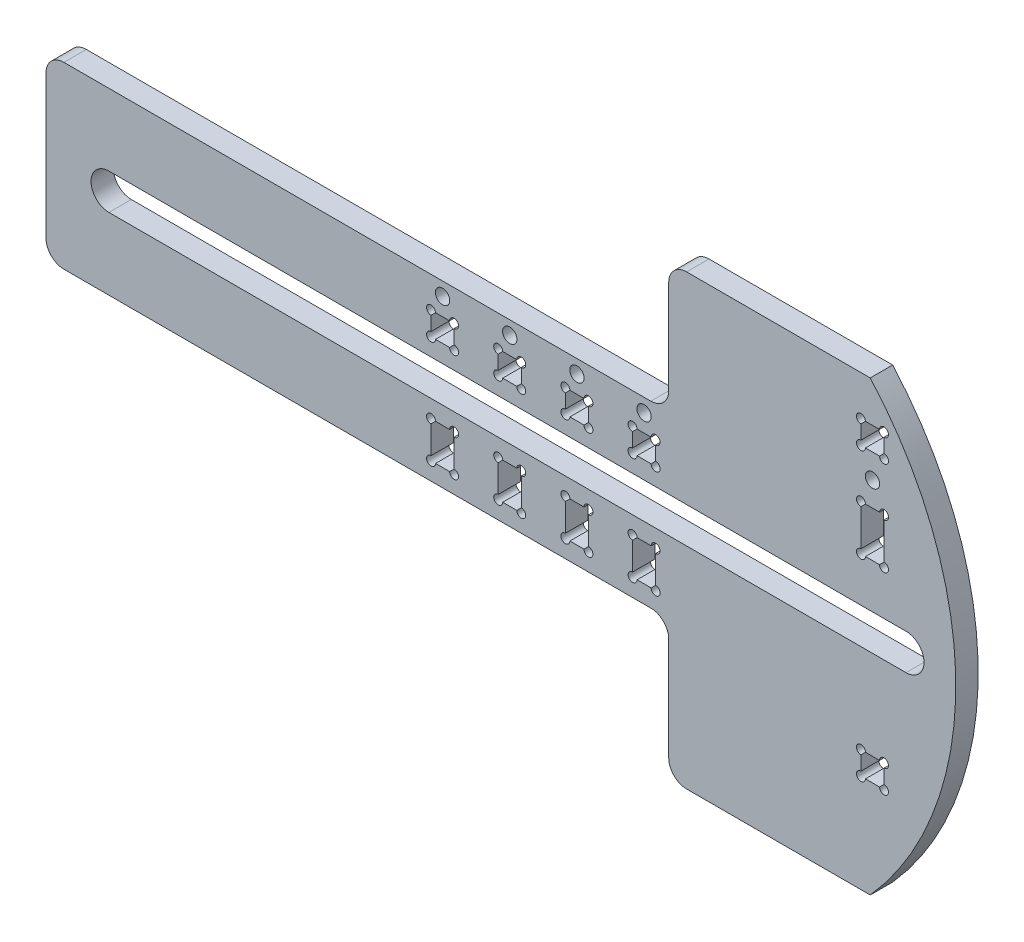
SolidWorks part; units mm, degrees
material "Somente - Acrílico Extrudado"
ref_plane "Front Plane" through (0, 0, 0) normal (0, 0, 1) x (1, 0, 0)
ref_plane "Top Plane" through (0, 0, 0) normal (0, 1, 0) x (1, 0, 0)
ref_plane "Right Plane" through (0, 0, 0) normal (1, 0, 0) x (0, 0, -1)
sketch "Esboço1" plane through (0, 0, 0) normal (0, 0, 1) x (1, 0, 0)
  line L181 (42.9065, -57.2479) -> (42.9065, -34.2586)
  line L182 (38.9065, -30.2586) -> (-92.1466, -30.2586)
  line L183 (-96.1466, -26.2586) -> (-96.1466, 5.7521)
  line L184 (-92.1466, 9.7521) -> (38.9065, 9.7521)
  line L185 (42.9065, 13.7521) -> (42.9065, 34.7521)
  line L186 (46.9065, 38.7521) -> (87.9065, 38.7521)
  line L187 (87.9065, -61.2479) -> (46.9065, -61.2479)
  line L188 (-82.0916, -6.2479) -> (95.9065, -6.2479)
  line L189 (95.9065, -14.2479) -> (-82.0935, -14.2479)
  line L190 (39.9815, 2.8271) -> (34.8315, 2.8271)
  line L191 (34.8315, 2.8271) -> (34.8315, -2.3229)
  line L192 (34.8315, -2.3229) -> (39.9815, -2.3229)
  line L193 (39.9815, -2.3229) -> (39.9815, 2.8271)
  line L194 (85.8315, 3.6771) -> (90.9815, 3.6771)
  line L195 (90.9815, 3.6771) -> (90.9815, 13.8271)
  line L196 (90.9815, 13.8271) -> (85.8315, 13.8271)
  line L197 (85.8315, 13.8271) -> (85.8315, 3.6771)
  line L198 (85.8315, -39.3229) -> (90.9815, -39.3229)
  line L199 (90.9815, -39.3229) -> (90.9815, -34.1729)
  line L200 (90.9815, -34.1729) -> (85.8315, -34.1729)
  line L201 (85.8315, -34.1729) -> (85.8315, -39.3229)
  line L202 (34.8315, -26.3229) -> (39.9815, -26.3229)
  line L203 (39.9815, -26.3229) -> (39.9815, -18.1729)
  line L204 (39.9815, -18.1729) -> (34.8315, -18.1729)
  line L205 (34.8315, -18.1729) -> (34.8315, -26.3229)
  line L206 (85.8315, 24.6771) -> (90.9815, 24.6771)
  line L207 (90.9815, 24.6771) -> (90.9815, 29.8271)
  line L208 (90.9815, 29.8271) -> (85.8315, 29.8271)
  line L209 (85.8315, 29.8271) -> (85.8315, 24.6771)
  line L210 (19.9065, -26.2479) -> (24.9065, -26.2479) construction
  line L211 (24.9065, -26.2479) -> (24.9065, -18.2479) construction
  line L212 (24.9065, -18.2479) -> (19.9065, -18.2479) construction
  line L213 (19.9065, -18.2479) -> (19.9065, -26.2479) construction
  line L214 (19.9065, -2.2479) -> (24.9065, -2.2479) construction
  line L215 (24.9065, -2.2479) -> (24.9065, 2.7521) construction
  line L216 (24.9065, 2.7521) -> (19.9065, 2.7521) construction
  line L217 (19.9065, 2.7521) -> (19.9065, -2.2479) construction
  line L218 (4.9065, 2.7521) -> (4.9065, -2.2479) construction
  line L219 (4.9065, -2.2479) -> (9.9065, -2.2479) construction
  line L220 (9.9065, -2.2479) -> (9.9065, 2.7521) construction
  line L221 (9.9065, 2.7521) -> (4.9065, 2.7521) construction
  line L222 (4.9065, -26.2479) -> (9.9065, -26.2479) construction
  line L223 (9.9065, -26.2479) -> (9.9065, -18.2479) construction
  line L224 (9.9065, -18.2479) -> (4.9065, -18.2479) construction
  line L225 (4.9065, -18.2479) -> (4.9065, -26.2479) construction
  line L226 (-10.0935, -26.2479) -> (-5.0935, -26.2479) construction
  line L227 (-5.0935, -26.2479) -> (-5.0935, -18.2479) construction
  line L228 (-5.0935, -18.2479) -> (-10.0935, -18.2479) construction
  line L229 (-10.0935, -18.2479) -> (-10.0935, -26.2479) construction
  line L230 (-10.0935, -2.2479) -> (-5.0935, -2.2479) construction
  line L231 (-5.0935, -2.2479) -> (-5.0935, 2.7521) construction
  line L232 (-5.0935, 2.7521) -> (-10.0935, 2.7521) construction
  line L233 (-10.0935, 2.7521) -> (-10.0935, -2.2479) construction
  line L234 (24.9815, 2.8271) -> (19.8315, 2.8271)
  line L235 (19.8315, 2.8271) -> (19.8315, -2.3229)
  line L236 (19.8315, -2.3229) -> (24.9815, -2.3229)
  line L237 (24.9815, -2.3229) -> (24.9815, 2.8271)
  line L238 (19.8315, -26.3229) -> (24.9815, -26.3229)
  line L239 (24.9815, -26.3229) -> (24.9815, -18.1729)
  line L240 (24.9815, -18.1729) -> (19.8315, -18.1729)
  line L241 (19.8315, -18.1729) -> (19.8315, -26.3229)
  line L242 (9.9815, 2.8271) -> (4.8315, 2.8271)
  line L243 (4.8315, 2.8271) -> (4.8315, -2.3229)
  line L244 (4.8315, -2.3229) -> (9.9815, -2.3229)
  line L245 (9.9815, -2.3229) -> (9.9815, 2.8271)
  line L246 (4.8315, -26.3229) -> (9.9815, -26.3229)
  line L247 (9.9815, -26.3229) -> (9.9815, -18.1729)
  line L248 (9.9815, -18.1729) -> (4.8315, -18.1729)
  line L249 (4.8315, -18.1729) -> (4.8315, -26.3229)
  line L250 (-5.0185, 2.8271) -> (-10.1685, 2.8271)
  line L251 (-10.1685, 2.8271) -> (-10.1685, -2.3229)
  line L252 (-10.1685, -2.3229) -> (-5.0185, -2.3229)
  line L253 (-5.0185, -2.3229) -> (-5.0185, 2.8271)
  line L254 (-10.1685, -26.3229) -> (-5.0185, -26.3229)
  line L255 (-5.0185, -26.3229) -> (-5.0185, -18.1729)
  line L256 (-5.0185, -18.1729) -> (-10.1685, -18.1729)
  line L257 (-10.1685, -18.1729) -> (-10.1685, -26.3229)
  circle A1 centre (7.4065, 6.7521) radius 1.5 construction
  circle A2 centre (22.4065, 6.7521) radius 1.5 construction
  circle A3 centre (-7.5935, 6.7521) radius 1.5 construction
  circle A4 centre (37.4065, 6.7521) radius 1.5
  arc A5 (42.9065, -34.2586) -> (38.9065, -30.2586) centre (38.9065, -34.2586) ccw
  arc A6 (-96.1466, -26.2586) -> (-92.1466, -30.2586) centre (-92.1466, -26.2586) ccw
  arc A7 (-92.1466, 9.7521) -> (-96.1466, 5.7521) centre (-92.1466, 5.7521) ccw
  arc A8 (38.9065, 9.7521) -> (42.9065, 13.7521) centre (38.9065, 13.7521) ccw
  arc A9 (46.9065, 38.7521) -> (42.9065, 34.7521) centre (46.9065, 34.7521) ccw
  arc A10 (87.9065, -61.2479) -> (87.9065, 38.7521) centre (32.0381, -11.2479) ccw
  arc A11 (42.9065, -57.2479) -> (46.9065, -61.2479) centre (46.9065, -57.2479) ccw
  arc A12 (-82.0916, -6.2479) -> (-82.0935, -14.2479) centre (-82.0935, -10.2479) ccw
  arc A13 (95.9065, -14.2479) -> (95.9065, -6.2479) centre (95.9065, -10.2479) ccw
  circle A14 centre (88.4065, 19.2521) radius 1.5
  circle A15 centre (22.4065, 6.7521) radius 1.5
  circle A16 centre (7.4065, 6.7521) radius 1.5
  circle A17 centre (-7.5935, 6.7521) radius 1.5
  dimension "D1" = 4
base flange "Flange-base1" sketch "Esboço1" thickness 5 reverse thickness direction no parameters "D1"=0.1
sketch "Esboço2" plane through (0, 0, 0) normal (0, 0, 1) x (1, 0, 0)
  line L0 (39.9815, -2.3229) -> (39.9815, 2.8271) construction
  line L1 (34.8315, -2.3229) -> (39.9815, -2.3229) construction
  circle A0 centre (90.9815, 29.8271) radius 1
  circle A1 centre (85.8315, 29.8271) radius 1
  circle A2 centre (85.8315, 24.6771) radius 1
  circle A3 centre (90.9815, 24.6771) radius 1
  circle A4 centre (90.9815, 13.8271) radius 1
  circle A5 centre (85.8315, 13.8271) radius 1
  circle A6 centre (90.9815, 3.6771) radius 1
  circle A7 centre (85.8315, 3.6771) radius 1
  circle A8 centre (85.8315, -34.1729) radius 1
  circle A9 centre (90.9815, -34.1729) radius 1
  circle A10 centre (90.9815, -39.3229) radius 1
  circle A11 centre (85.8315, -39.3229) radius 1
  circle A12 centre (34.8315, 2.8271) radius 1
  circle A13 centre (39.9815, 2.8271) radius 1
  circle A14 centre (39.9815, -2.3229) radius 1
  circle A15 centre (34.8315, -2.3229) radius 1
  circle A16 centre (34.8315, -18.1729) radius 1
  circle A17 centre (39.9815, -18.1729) radius 1
  circle A18 centre (39.9815, -26.3229) radius 1
  circle A19 centre (34.8315, -26.3229) radius 1
  circle A20 centre (19.8315, 2.8271) radius 1
  circle A21 centre (24.9815, 2.8271) radius 1
  circle A22 centre (24.9815, -2.3229) radius 1
  circle A23 centre (19.8315, -2.3229) radius 1
  circle A24 centre (19.8315, -18.1729) radius 1
  circle A25 centre (24.9815, -18.1729) radius 1
  circle A26 centre (24.9815, -26.3229) radius 1
  circle A27 centre (19.8315, -26.3229) radius 1
  circle A28 centre (4.8315, 2.8271) radius 1
  circle A29 centre (9.9815, 2.8271) radius 1
  circle A30 centre (9.9815, -2.3229) radius 1
  circle A31 centre (4.8315, -2.3229) radius 1
  circle A32 centre (4.8315, -18.1729) radius 1
  circle A33 centre (9.9815, -18.1729) radius 1
  circle A34 centre (9.9815, -26.3229) radius 1
  circle A35 centre (4.8315, -26.3229) radius 1
  circle A36 centre (-10.1685, 2.8271) radius 1
  circle A37 centre (-5.0185, 2.8271) radius 1
  circle A38 centre (-5.0185, -2.3229) radius 1
  circle A39 centre (-10.1685, -2.3229) radius 1
  circle A40 centre (-10.1685, -18.1729) radius 1
  circle A41 centre (-5.0185, -18.1729) radius 1
  circle A42 centre (-5.0185, -26.3229) radius 1
  circle A43 centre (-10.1685, -26.3229) radius 1
  dimension "D1" = 2
  dimension "D2" = 4
extrude "Corte-extrusão1" cut sketch "Esboço2" against normal up to next (5 mm away)
sketch "Esboço3" plane through (0, 0, 0) normal (0, 0, 1) x (1, 0, 0)
  circle A0 centre (88.4065, 19.2521) radius 1.6
  circle A1 centre (37.4065, 6.7521) radius 1.6
  circle A2 centre (22.4065, 6.7521) radius 1.6
  circle A3 centre (7.4065, 6.7521) radius 1.6
  circle A4 centre (-7.5935, 6.7521) radius 1.6
  dimension "D1" = 3.2
  dimension "D2" = 4
extrude "Corte-extrusão2" cut sketch "Esboço3" against normal up to next
sketch "Curva-Linhas1" [suppressed] plane through (0, 0, 0) normal (0, 1, 0) x (1, 0, 0)
sketch "Caixa delimitadora1" [suppressed] plane through (0, 0, 0) normal (0, 1, 0) x (1, 0, 0)
sheet metal parameters "Chapa metálica6" thickness 5 parameters "D1"=0.1
flat pattern "Padrão-Plano6" [suppressed]
sketch "Curva-Linhas2" plane through (0, 0, 0) normal (0, 1, 0) x (1, 0, 0)
sketch3d "Caixa delimitadora2" [suppressed]
  line L0 (-143.0531, 96, 0) -> (60.1068, 96, 0) construction
  line L1 (-143.0531, -4, 0) -> (60.1068, -4, 0) construction
  line L2 (-143.0531, 96, 0) -> (-143.0531, -4, 0) construction
  line L3 (60.1068, 96, 0) -> (60.1068, -4, 0) construction
sheet metal parameters "Chapa metálica7" thickness 5 parameters "D1"=0.1
flat pattern "Padrão-Plano6"
sketch "Curva-Linhas2" plane through (0, 0, 0) normal (0, 1, 0) x (1, 0, 0)
sketch3d "Caixa delimitadora2" [suppressed]
  line L0 (-143.0531, 96, 0) -> (60.1068, 96, 0) construction
  line L1 (-143.0531, -4, 0) -> (60.1068, -4, 0) construction
  line L2 (-143.0531, 96, 0) -> (-143.0531, -4, 0) construction
  line L3 (60.1068, 96, 0) -> (60.1068, -4, 0) construction
sheet metal parameters "Chapa metálica8" thickness 5 parameters "D1"=0.1
flat pattern "Padrão-Plano6"
sketch "Curva-Linhas2" plane through (0, 0, 0) normal (0, 1, 0) x (1, 0, 0)
sketch3d "Caixa delimitadora2" [suppressed]
  line L0 (-143.0531, 96, 0) -> (60.1068, 96, 0) construction
  line L1 (-143.0531, -4, 0) -> (60.1068, -4, 0) construction
  line L2 (-143.0531, 96, 0) -> (-143.0531, -4, 0) construction
  line L3 (60.1068, 96, 0) -> (60.1068, -4, 0) construction
